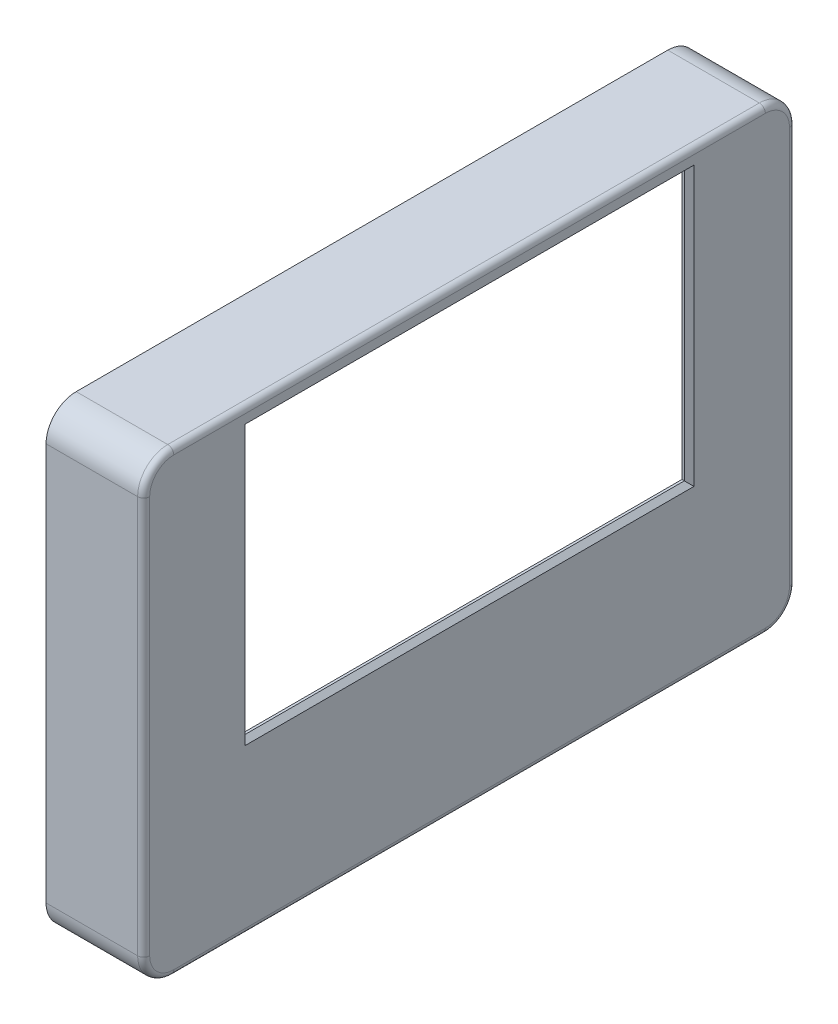
SolidWorks part; units mm, degrees
ref_plane "Front Plane" through (0, 0, 0) normal (1, 0, 0) x (0, 1, 0)
ref_plane "Top Plane" through (0, 0, 0) normal (0, 0, 1) x (0, 1, 0)
ref_plane "Right Plane" through (0, 0, 0) normal (0, 1, 0) x (-1, 0, 0)
sketch "Sketch2" plane through (0, 0, 0) normal (1, 0, 0) x (0, 1, 0)
  line L0 (-0.6816, 40.45) -> (-48.2816, 40.45) construction
  line L1 (-3.8816, 47.5) -> (-45.0816, 47.5) construction
  line L2 (1.1184, 56.6) -> (-74.8816, 56.6)
  line L3 (1.1184, 56.6) -> (1.1184, -51.6)
  line L4 (1.1184, -51.6) -> (-74.8816, -51.6)
  line L5 (-74.8816, 56.6) -> (-74.8816, -51.6)
  line L6 (-45.0816, -47.5) -> (-3.8816, -47.5) construction
  line L7 (-0.6816, -40.45) -> (-0.6816, 40.45) construction
  line L8 (-48.2816, 40.45) -> (-48.2816, -40.45) construction
  line L9 (-48.2816, -40.45) -> (-0.6816, -40.45) construction
  line L10 (-46.7816, 38.95) -> (-2.1816, 38.95)
  line L11 (-46.7816, 38.95) -> (-46.7816, -33.95)
  line L12 (-46.7816, -33.95) -> (-2.1816, -33.95)
  line L13 (-2.1816, 38.95) -> (-2.1816, -33.95)
  dimension "D1" = 9.1
  dimension "D2" = 4.1
  dimension "D3" = 1.8
  dimension "D4" = 26.6
  dimension "D5" = 1.5
  dimension "D6" = 1.5
  dimension "D7" = 1.5
  dimension "D8" = 6.5
extrude "Boss-Extrude1" add sketch "Sketch2" against normal blind 15 and the other way blind 1.2 contours L3 L2 L5 L4
fillet "Fillet1" radius 5 4 edges at (-6.9, -74.8816, 56.6) (-6.9, -74.8816, -51.6) (-6.9, 1.1184, -51.6) (-6.9, 1.1184, 56.6)
fillet "Fillet2" radius 1 8 edges at (1.2, -0.346, 55.1355) (1.2, -36.8816, 56.6) (1.2, -73.4171, 55.1355) (1.2, -74.8816, 2.5) (1.2, -73.4171, -50.1355) (1.2, -36.8816, -51.6) (1.2, -0.346, -50.1355) (1.2, 1.1184, 2.5)
shell "Shell1" thickness 1.65 removed face at (-15, -36.8816, 2.5)
extrude "Cut-Extrude1" cut sketch "Sketch2<3>" along normal through all contours L13 L10 L11 L12 region at (0, -24.4816, 2.5)
sketch "Sketch2<3>" plane through (0, 0, 0) normal (1, 0, 0) x (0, 1, 0) same geometry as "Sketch2"
chamfer "Chamfer1" distance 0.8 angle 45 4 edges at (1.2, -24.4816, 38.95) (1.2, -2.1816, 2.5) (1.2, -24.4816, -33.95) (1.2, -46.7816, 2.5)
sketch "Sketch3" plane through (0, 0, 0) normal (-1, 0, 0) x (0, -1, 0)
  circle A0 centre (45.0816, -44.3) radius 1.5
  circle A1 centre (3.8816, -44.3) radius 1.5
  circle A2 centre (45.0816, 44.3) radius 1.5
  circle A3 centre (3.8816, 44.3) radius 1.5
  circle A4 centre (3.8816, 44.3) radius 3
  circle A5 centre (3.8816, 44.3) radius 1.6 construction
  circle A6 centre (45.0816, 44.3) radius 3
  circle A7 centre (45.0816, -44.3) radius 3
  circle A8 centre (3.8816, -44.3) radius 3
  dimension "D1" = 3
  dimension "D2" = 6
extrude "Boss-Extrude2" add sketch "Sketch3" along normal blind 4
fillet "Fillet3" radius 1 4 edges at (0, -3.8816, 41.3) (0, -45.0816, 41.3) (0, -45.0816, -47.3) (0, -3.8816, -47.3)
fillet "Fillet4" radius 0.4 8 edges at (-4, -45.0816, 47.3) (-4, -45.0816, 45.8) (-4, -3.8816, 45.8) (-4, -3.8816, 47.3) (-4, -3.8816, -42.8) (-4, -3.8816, -41.3) (-4, -45.0816, -41.3) (-4, -45.0816, -42.8)
equation "\"D1@Sketch2\"=7.5+1.6"
equation "\"D2@Sketch2\"=\"D1@Sketch2\" - 5"
equation "\"D4@Sketch2\"=25+1.6"
